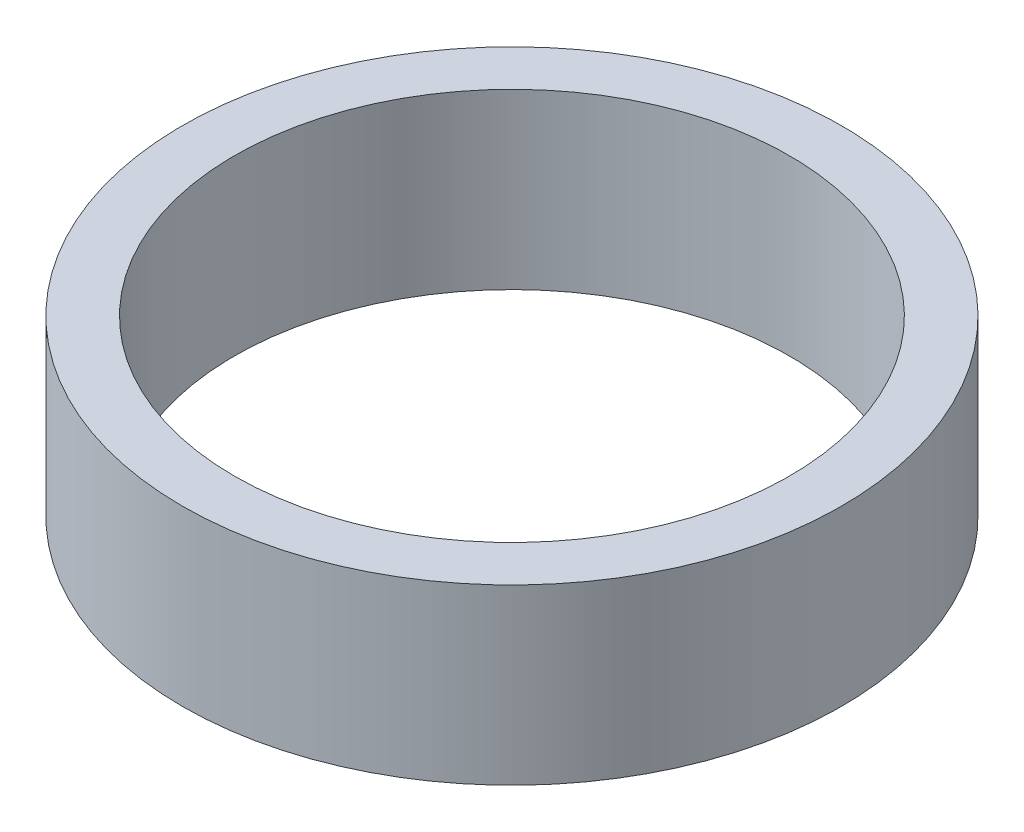
SolidWorks part; units mm, degrees
ref_plane "Front Plane" through (0, 0, 0) normal (0, 0, 1) x (1, 0, 0)
ref_plane "Top Plane" through (0, 0, 0) normal (0, 1, 0) x (1, 0, 0)
ref_plane "Right Plane" through (0, 0, 0) normal (1, 0, 0) x (0, 0, -1)
sketch "Sketch1" plane through (0, 0, 0) normal (0, 1, 0) x (1, 0, 0)
  circle A0 centre (0, 0) radius 47.5
  dimension "FLANGE_OD" = 95
extrude "Boss-Extrude1" add sketch "Sketch1" along normal blind 25
sketch "Sketch2" plane through (0, 0, 0) normal (0, 1, 0) x (1, 0, 0)
  circle A0 centre (0, 0) radius 40
  dimension "BORE_D" = 80
extrude "Cut-Extrude1" cut sketch "Sketch2" along normal through all
sketch "Sketch3" plane through (0, 25, 0) normal (0, 1, 0) x (1, 0, 0)
  circle A0 centre (0, 0) radius 21.5023 construction
  circle A1 centre (-21.5023, 0) radius 1.5
  dimension "BOLT_D" = 3
  dimension "BOLT_PCD" = 43.0046
extrude "Cut-Extrude2" cut sketch "Sketch3" against normal blind 15.3026 rebuild error yes
pattern_circular "CirPattern1" count 6 over 360 rebuild error yes
